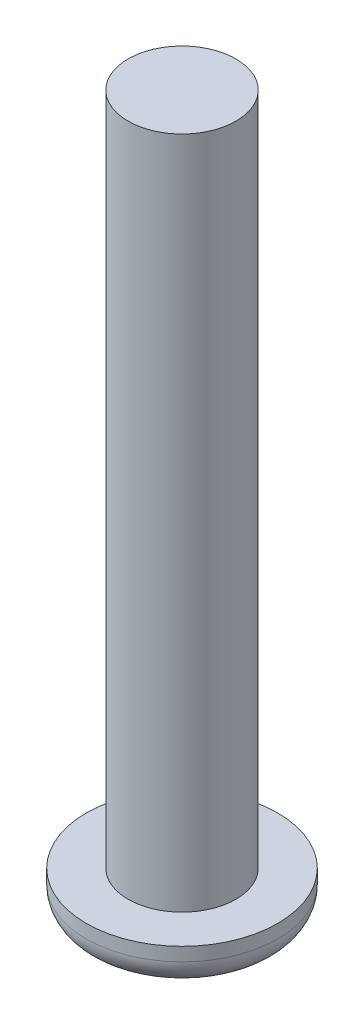
SolidWorks part; units mm, degrees
ref_plane "Front Plane" through (0, 0, 0) normal (0, 0, 1) x (1, 0, 0)
ref_plane "Top Plane" through (0, 0, 0) normal (0, 1, 0) x (1, 0, 0)
ref_plane "Right Plane" through (0, 0, 0) normal (1, 0, 0) x (0, 0, -1)
sketch "Sketch1" plane through (0, 0, 0) normal (0, 1, 0) x (1, 0, 0)
  circle A0 centre (0, 0) radius 4
  dimension "D1" = 8
extrude "Boss-Extrude1" add sketch "Sketch1" along normal blind 50 contours A0
sketch "Sketch2" plane through (0, 0, 0) normal (0, -1, 0) x (1, 0, 0)
  circle A0 centre (0, 0) radius 7.1
  circle A1 centre (0, 0) radius 4 construction
  circle A2 centre (0, 0) radius 4 construction
  dimension "D1" = 14.2
extrude "Boss-Extrude2" add sketch "Sketch2" along normal blind 3
fillet "Fillet1" radius 2 1 edges at (0, -3, -7.1)
sketch "Sketch3" plane through (0, -3, 0) normal (0, -1, 0) x (1, 0, 0)
  line L0 (0.375, 0.375) -> (1.5, 0.375)
  line L1 (-0.375, -1.5) -> (0.375, -1.5)
  line L2 (-0.375, -1.5) -> (-0.375, -0.375)
  line L3 (-0.375, 1.5) -> (0.375, 1.5)
  line L4 (0.375, -1.5) -> (0.375, -0.375)
  line L7 (-1.5, -0.375) -> (-0.375, -0.375)
  line L8 (-1.5, -0.375) -> (-1.5, 0.375)
  line L9 (-1.5, 0.375) -> (-0.375, 0.375)
  line L10 (1.5, -0.375) -> (1.5, 0.375)
  line L15 (0.375, 0.375) -> (0.375, 1.5)
  line L16 (0.375, -0.375) -> (1.5, -0.375)
  line L17 (-0.375, 0.375) -> (-0.375, 1.5)
  point P0 (0, 0)
  point P6 (0, 0)
  dimension "D1" = 3
  dimension "D2" = 0.75
extrude "Cut-Extrude1" cut sketch "Sketch3" against normal blind 1 draft 15
sketch "Sketch5" [suppressed] plane through (0, 0, 0) normal (0, 0, 1) x (1, 0, 0)
  line L0 (-2.1, -2) -> (2.1, -2) construction
  line L3 (0, 0) -> (0, 24) construction
  point P6 (0, 11)
  dimension "D1" = 13
  dimension "D2" = 26
sketch "Sketch6" plane through (0, 0, 0) normal (0, 0, 1) x (1, 0, 0)
  line L0 (0, 0) -> (0, 50) construction
  line L1 (4, 50) -> (-4, 50) construction
